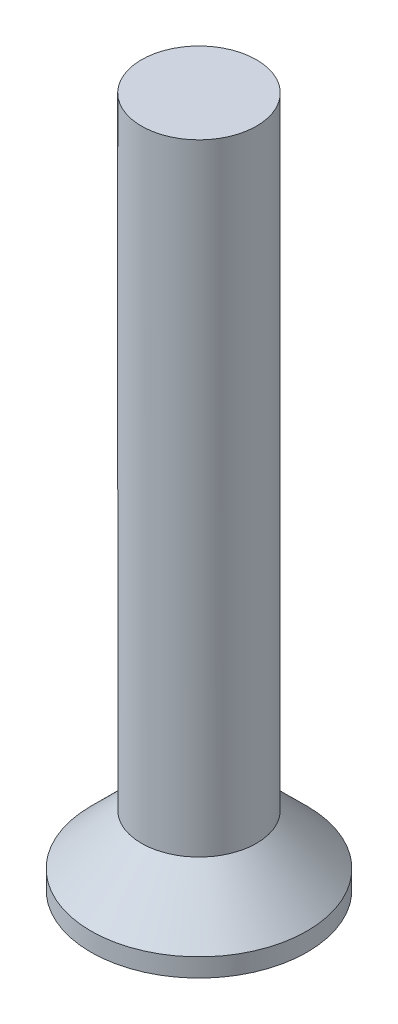
SolidWorks part; units mm, degrees
material "Nylon 101"
ref_plane "Front Plane" through (0, 0, 0) normal (0, 0, 1) x (1, 0, 0)
ref_plane "Top Plane" through (0, 0, 0) normal (0, 1, 0) x (1, 0, 0)
ref_plane "Right Plane" through (0, 0, 0) normal (1, 0, 0) x (0, 0, -1)
sketch "Sketch1" plane through (0, 0, 0) normal (0, 1, 0) x (1, 0, 0)
  circle A0 centre (0, 0) radius 2.35
  dimension "D1" = 4.7
extrude "Boss-Extrude1" add sketch "Sketch1" along normal blind 1.5
sketch "Sketch2" plane through (0, 0, 0) normal (0, -1, 0) x (1, 0, 0)
  circle A0 centre (0, 0) radius 1.25
  dimension "D1" = 2.5
extrude "Boss-Extrude2" add sketch "Sketch2" against normal blind 15
chamfer "Chamfer1" distance 1.1 angle 45 1 edges at (0, 1.5, 2.35)
sketch "Sketch3" plane through (0, 0, 0) normal (0, -1, 0) x (1, 0, 0)
  line L0 (-0.25, 1.5) -> (-0.25, 0.25)
  line L1 (1.5, -0.25) -> (-1.5, -0.25) construction
  line L2 (1.5, -0.25) -> (1.5, 0.25) construction
  line L3 (1.5, 0.25) -> (-1.5, 0.25) construction
  line L4 (-1.5, -0.25) -> (-1.5, 0.25) construction
  line L5 (1.5, -0.25) -> (-1.5, 0.25) construction
  line L6 (1.5, 0.25) -> (-1.5, -0.25) construction
  line L7 (-0.25, -1.5) -> (0.25, -1.5) construction
  line L8 (-0.25, -1.5) -> (-0.25, 1.5) construction
  line L9 (-0.25, 1.5) -> (0.25, 1.5) construction
  line L10 (0.25, -1.5) -> (0.25, 1.5) construction
  line L11 (-0.25, -1.5) -> (0.25, 1.5) construction
  line L12 (-0.25, 1.5) -> (0.25, -1.5) construction
  line L13 (-0.25, 0.25) -> (-1.5, 0.25)
  line L14 (-1.5, 0.25) -> (-1.5, -0.25)
  line L15 (-1.5, -0.25) -> (-0.25, -0.25)
  line L16 (-0.25, -0.25) -> (-0.25, -1.5)
  line L17 (-0.25, -1.5) -> (0.25, -1.5)
  line L18 (0.25, -1.5) -> (0.25, -0.25)
  line L19 (0.25, -0.25) -> (1.5, -0.25)
  line L20 (1.5, -0.25) -> (1.5, 0.25)
  line L21 (1.5, 0.25) -> (0.25, 0.25)
  line L22 (0.25, 0.25) -> (0.25, 1.5)
  line L23 (-0.25, 1.5) -> (0.25, 1.5)
  point P0 (0, 0)
  point P6 (0, 0)
  dimension "D1" = 3
  dimension "D2" = 0.5
extrude "Cut-Extrude1" cut sketch "Sketch3" against normal blind 0.3
